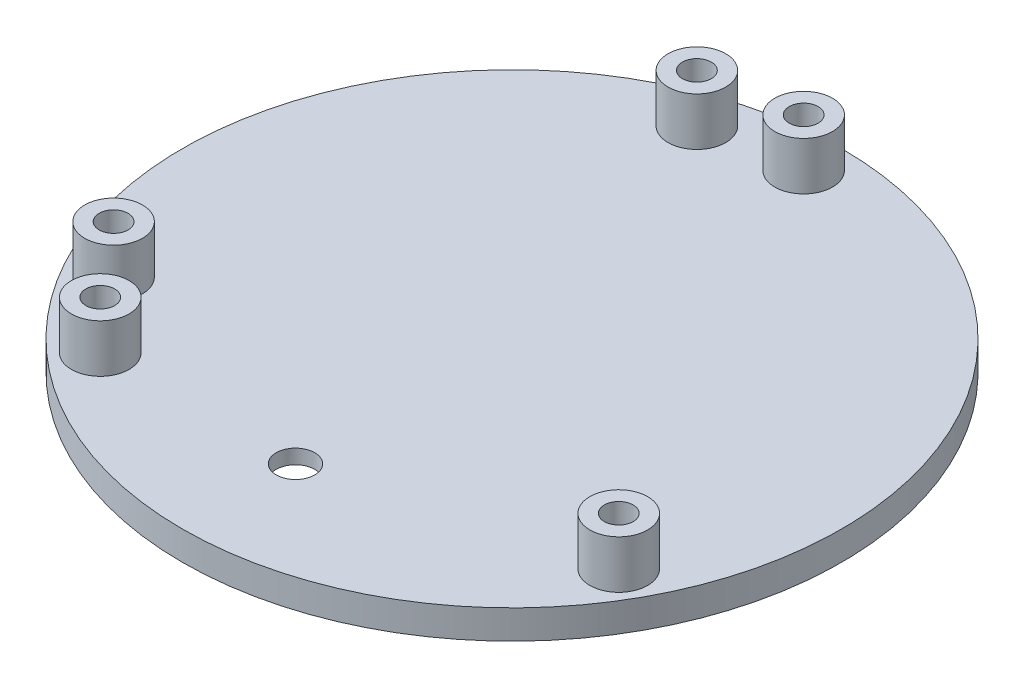
SolidWorks part; units mm, degrees
material "ABS"
ref_plane "Front Plane" through (0, 0, 0) normal (0, 0, 1) x (1, 0, 0)
ref_plane "Top Plane" through (0, 0, 0) normal (0, 1, 0) x (1, 0, 0)
ref_plane "Right Plane" through (0, 0, 0) normal (1, 0, 0) x (0, 0, -1)
sketch "Sketch1" plane through (0, 0, 0) normal (0, 0, 1) x (1, 0, 0)
  line L0 (0, 0) -> (68.5, 0)
  line L1 (68.5, 0) -> (68.5, -6)
  line L2 (68.5, -6) -> (66.5, -6)
  line L3 (66.5, -6) -> (66.5, -3)
  line L5 (53.5, -3) -> (53.5, -6)
  line L6 (53.5, -6) -> (50.5, -6)
  line L7 (50.5, -6) -> (50.5, -3)
  line L8 (50.5, -3) -> (6, -3)
  line L9 (6, -3) -> (6, -5)
  line L10 (6, -5) -> (0, -5)
  line L11 (0, -5) -> (0, 0)
  line L12 (62.3516, -3) -> (66.5, -3)
  line L13 (57.6484, -3) -> (53.5, -3)
  arc A0 (62.3516, -3) -> (57.6484, -3) centre (60, -6.6) ccw
  point P4 (67.5, -6)
  dimension "D2" = 4.3
  dimension "D1" = 60
  dimension "D3" = 6.5
  dimension "D4" = 3
  dimension "D5" = 6.5
  dimension "D6" = 3
  dimension "D7" = 2
  dimension "D8" = 50.5
  dimension "D9" = 0.6
  dimension "D10" = 5
  dimension "D11" = 6
revolve "Revolve1" add sketch "Sketch1" angle 360 about L11
sketch "Sketch2" plane through (0, 0, 0) normal (0, 1, 0) x (1, 0, 0)
  line L0 (-52.5, -30.3109) -> (0, 60.6218) construction
  line L1 (0, 60.6218) -> (52.5, -30.3109) construction
  line L2 (52.5, -30.3109) -> (-52.5, -30.3109) construction
  line L3 (0, 0) -> (0, 60.6218) construction
  line L4 (0, 0) -> (52.5, -30.3109) construction
  line L5 (0, 0) -> (-52.5, -30.3109) construction
  line L6 (0, 0) -> (0, -45) construction
  line L7 (-40.2731, -45.3109) -> (-40.2731, -30.3109) construction
  line L8 (-19.1038, 57.533) -> (-6.1134, 50.033) construction
  circle A0 centre (0, 60.6218) radius 6
  circle A1 centre (0, 60.6218) radius 3
  circle A2 centre (52.5, -30.3109) radius 6
  circle A3 centre (-52.5, -30.3109) radius 6
  circle A4 centre (-52.5, -30.3109) radius 3
  circle A5 centre (52.5, -30.3109) radius 3
  circle A6 centre (0, -45) radius 4 construction
  arc A7 (0, 60.6218) -> (-24.7136, -55.3555) centre (0, 0) ccw construction
  circle A8 centre (-40.2731, -45.3109) radius 6
  circle A9 centre (-19.1038, 57.533) radius 6
  circle A10 centre (-40.2731, -45.3109) radius 3
  circle A11 centre (-19.1038, 57.533) radius 3
  dimension "D2" = 12
  dimension "D3" = 6
  dimension "D5" = 8
  dimension "D6" = 12
  dimension "D8" = 6
  dimension "D1" = 105
  dimension "D4" = 45
  dimension "D7" = 15
extrude "Boss-Extrude1" add sketch "Sketch2" along normal blind 10
sketch "Sketch3" plane through (0, 0, 0) normal (0, 1, 0) x (1, 0, 0)
  circle A0 centre (0, -45) radius 4
  circle A1 centre (0, -45) radius 4 construction
extrude "Cut-Extrude1" cut sketch "Sketch3" against normal blind 10
